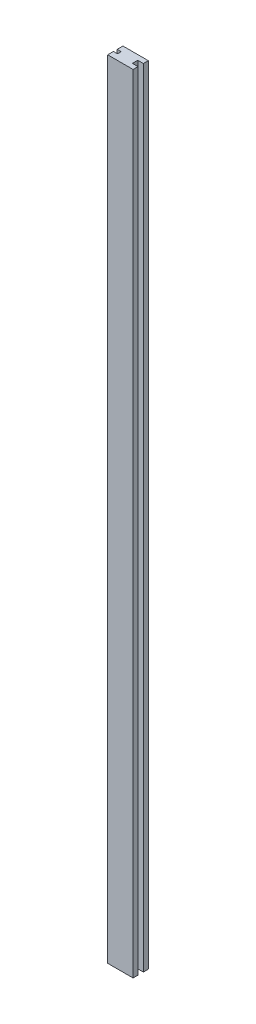
SolidWorks part; units mm, degrees
ref_plane "Спереди" through (0, 0, 0) normal (0, 0, 1) x (1, 0, 0)
ref_plane "Сверху" through (0, 0, 0) normal (0, 1, 0) x (1, 0, 0)
ref_plane "Справа" through (0, 0, 0) normal (1, 0, 0) x (0, 0, -1)
sketch "Эскиз1" plane through (0, 0, 0) normal (0, 1, 0) x (1, 0, 0)
  line L0 (0, 3.6577) -> (0, -3.6577)
  line L1 (0, -3.6577) -> (-7.957, -3.6577)
  line L2 (-7.957, -3.6577) -> (-7.957, -15)
  line L3 (-7.957, -15) -> (42.043, -15)
  line L4 (42.043, -15) -> (42.043, -5.25)
  line L5 (42.043, -5.25) -> (31, -5.25)
  line L6 (31, -5.25) -> (31, 0)
  line L7 (-18.9883, 0) -> (46.2952, 0) construction
  line L11 (31, 5.25) -> (31, 0)
  line L12 (42.043, 5.25) -> (31, 5.25)
  line L13 (42.043, 15) -> (42.043, 5.25)
  line L14 (-7.957, 15) -> (42.043, 15)
  line L15 (-7.957, 3.6577) -> (-7.957, 15)
  line L16 (0, 3.6577) -> (-7.957, 3.6577)
  point P0 (35.7611, 0)
  point P21 (0, 0)
extrude "Бобышка-Вытянуть1" add sketch "Эскиз1" along normal blind 1550
